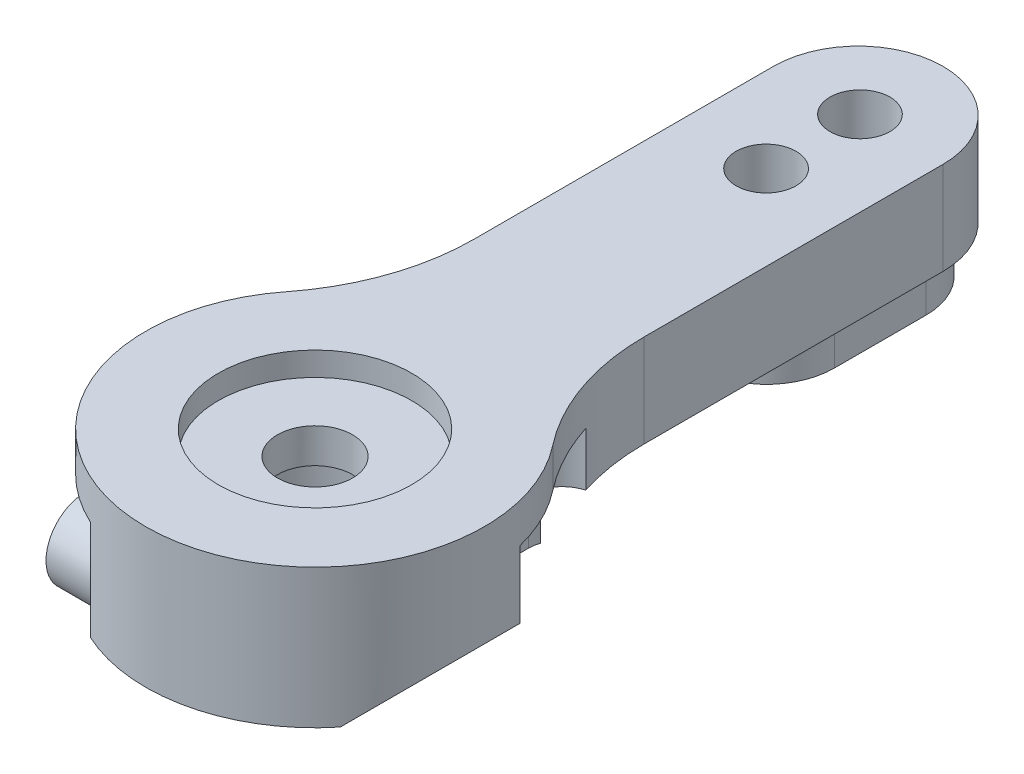
SolidWorks part; units mm, degrees
ref_plane "Front Plane" through (0, 0, 0) normal (0, 0, 1) x (1, 0, 0)
ref_plane "Top Plane" through (0, 0, 0) normal (0, 1, 0) x (1, 0, 0)
ref_plane "Right Plane" through (0, 0, 0) normal (1, 0, 0) x (0, 0, -1)
sketch "Sketch1" plane through (0, 0, 0) normal (0, 1, 0) x (1, 0, 0)
  line L0 (0, 24.015) -> (0, 0) construction
  line L1 (3.75, 24.015) -> (3.75, 0)
  line L2 (-3.75, 24.015) -> (-3.75, 0)
  line L3 (0, 24.015) -> (0, 19.955) construction
  line L4 (3, 24.015) -> (3, 19.955)
  line L5 (-3, 24.015) -> (-3, 19.955)
  circle A0 centre (0, 0) radius 7.485
  arc A1 (3.75, 24.015) -> (-3.75, 24.015) centre (0, 24.015) ccw
  arc A2 (-3.75, 0) -> (3.75, 0) centre (0, 0) ccw
  arc A3 (3, 24.015) -> (-3, 24.015) centre (0, 24.015) ccw
  arc A4 (-3, 19.955) -> (3, 19.955) centre (0, 19.955) ccw
  point P3 (0, 12.0075)
  point P11 (0, 21.985)
  dimension "D2" = 14.97
  dimension "D1" = 7.5
  dimension "D3" = 24.015
  dimension "D4" = 6
  dimension "D5" = 4.06
extrude "Boss-Extrude1" add sketch "Sketch1" along normal blind 2.05 contours A2 L2 A0 L1 | L5 A4 L4 A3 | L2 A2 L1 A0 region at (6.307, 0, -3.6365) region at (0, 0, -2.0765) region at (0, 0, -21.985)
extrude "Boss-Extrude2" add sketch "Sketch1<3>" along normal blind 4.1 from surface contours A2 L2 A0 L1 | L2 A2 L1 A0 | L1 A1 L2 A0 A4 L5 A3 L4 | L5 A4 L4 A3 region at (0, 0, -14.3795) region at (6.307, 0, -3.6365) region at (0, 0, -2.0765) region at (0, 0, -21.985) starting at face at (0, 2.05, -21.985)
sketch "Sketch1<3>" plane through (0, 0, 0) normal (0, 1, 0) x (1, 0, 0) same geometry as "Sketch1"
fillet "Fillet1" radius 10 2 edges at (-3.75, 4.1, -6.4779) (3.75, 4.1, -6.4779)
sketch "Sketch2" plane through (0, 6.15, 0) normal (0, 1, 0) x (1, 0, 0)
  circle A0 centre (0, 0) radius 1.66
  circle A1 centre (0, 0) radius 4.275
  dimension "D1" = 3.32
  dimension "D2" = 8.55
extrude "Cut-Extrude1" cut sketch "Sketch2" against normal through all contours A0 region at (0, 6.15, 0)
extrude "Cut-Extrude2" cut sketch "Sketch2<3>" against normal blind 1.05 contours A1 A0 region at (-4.1541, 6.15, 0)
sketch "Sketch2<3>" plane through (0, 6.15, 0) normal (0, 1, 0) x (1, 0, 0) same geometry as "Sketch2"
sketch "Sketch3" plane through (0, 0, 0) normal (0, -1, 0) x (-1, 0, 0)
  circle A0 centre (0, 19.94) radius 1.325
  circle A1 centre (0, 24.09) radius 1.325
  circle A2 centre (0, 0) radius 7.485 construction
  dimension "D1" = 2.65
  dimension "D2" = 4.15
  dimension "D3" = 24.09
extrude "Cut-Extrude3" cut sketch "Sketch3" against normal through all
sketch "Sketch4" plane through (0, 0, 0) normal (0, 0, 1) x (1, 0, 0)
  line L0 (5.8233, 0) -> (7.485, 1.6617)
  line L1 (-7.485, 0) -> (7.485, 0) construction
  line L2 (7.485, 0) -> (7.485, 6.15) construction
  dimension "D1" = 2.35
  dimension "D2" = 45
extrude "Cut-Extrude4" cut sketch "Sketch4" against normal through all and the other way through all flip side to cut
mirror "Mirror1" about plane through (0, 0, 0) normal (1, 0, 0) of "Cut-Extrude4"
sketch "Sketch5" plane through (0, 0, 0) normal (0, -1, 0) x (1, 0, 0)
  line L1 (21.7205, -1.7974) -> (4.635, -1.7974)
  line L2 (21.7205, -1.7974) -> (21.7205, -7.7974)
  line L3 (21.7205, -7.7974) -> (4.635, -7.7974)
  line L4 (3.135, -3.2974) -> (3.135, -6.2974)
  line L10 (-4.635, 1.7974) -> (-13.9063, 1.7974)
  line L11 (-3.135, 3.2974) -> (-3.135, 10.5078)
  line L12 (-3.135, 10.5078) -> (-13.9063, 10.5078)
  line L13 (-13.9063, 1.7974) -> (-13.9063, 10.5078)
  arc A0 (4.635, -7.7974) -> (3.135, -6.2974) centre (4.635, -6.2974) cw
  arc A1 (4.635, -1.7974) -> (3.135, -3.2974) centre (4.635, -3.2974) ccw
  arc A4 (-4.635, 1.7974) -> (-3.135, 3.2974) centre (-4.635, 3.2974) ccw
  dimension "D1" = 1.5
  dimension "D5" = 1.5
  dimension "D2" = 3
  dimension "D3" = 3.135
  dimension "D4" = 6.5
  dimension "D6" = 6.5
  dimension "D7" = 3.135
extrude "Cut-Extrude5" cut sketch "Sketch5" against normal blind 4.42
sketch "Sketch6" plane through (0, 0, 0) normal (0, -1, 0) x (1, 0, 0)
  circle A0 centre (0, 0) radius 3
  dimension "D1" = 6
extrude "Cut-Extrude6" cut sketch "Sketch6" against normal blind 3.57
sketch "Sketch7" plane through (-3.135, 0, 0) normal (-1, 0, 0) x (0, 0, 1)
  line L1 (1.7974, 4.42) -> (1.7974, 0) construction
  line L2 (3.2974, 4.42) -> (6.7968, 4.42) construction
  circle A0 centre (4.9974, 1.92) radius 1.76
  dimension "D1" = 3.52
  dimension "D2" = 3.2
  dimension "D3" = 2.5
extrude "Boss-Extrude3" add sketch "Sketch7" along normal blind 2
equation "\"D3@Sketch1\"=35.25-\"D1@Sketch1\"/2-\"D2@Sketch1\"/2"
equation "\"D5@Sketch1\"=10.06-\"D4@Sketch1\""
equation "\"D2@Sketch3\"=1.5+\"D1@Sketch3\""
equation "\"D3@Sketch3\"=30.25+\"D1@Sketch3\"/2-14.97/2"
equation "\"D3@Sketch5\"=2.58+1.11/2"
equation "\"D6@Sketch5\"=\"D4@Sketch5\""
equation "\"D7@Sketch5\"=\"D3@Sketch5\""
